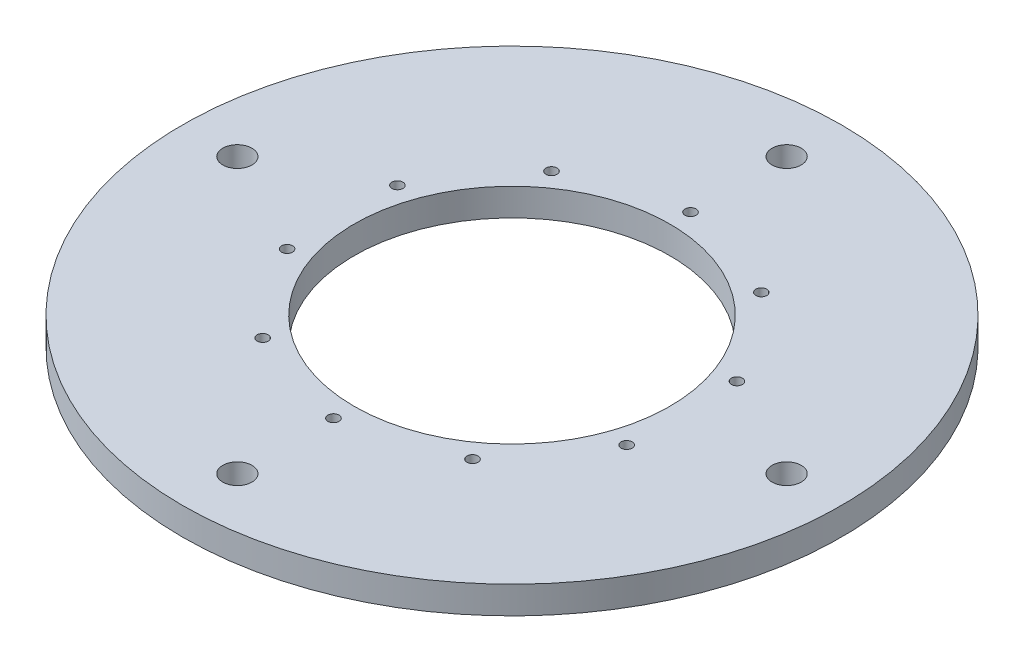
SolidWorks part; units mm, degrees
material "Plain Carbon Steel"
ref_plane "Front Plane" through (0, 0, 0) normal (0, 0, 1) x (1, 0, 0)
ref_plane "Top Plane" through (0, 0, 0) normal (0, 1, 0) x (1, 0, 0)
ref_plane "Right Plane" through (0, 0, 0) normal (1, 0, 0) x (0, 0, -1)
sketch "Sketch1" plane through (0, 0, 0) normal (0, 1, 0) x (1, 0, 0)
  circle A3 centre (0, 0) radius 152.4
  circle A8 centre (0, 0) radius 127 construction
  circle A20 centre (0, 0) radius 73.025
  circle A23 centre (0, 0) radius 82.55 construction
  point P2 (0, 127)
  point P5 (0, 82.55)
  dimension "Diameter_Takeout_BoltCircle" = 254
  dimension "Diameter_ThrustPlate" = 304.8
  dimension "D2" = 165.1
  dimension "D4" = 146.05
extrude "ThrustPlate_TC3" add sketch "Sketch1" against normal blind 12.7 separate body contours A3 region at (-148.0895, 0, 0)
sketch "Sketch11" plane through (0, 0, 0) normal (0, 1, 0) x (1, 0, 0)
  point P0 (0, 127)
hole_wizard "UNDEF_Clearance_ThrustPlate" positions "Sketch11" profile "Sketch12" hole size "1/2" standard "ANSI Inch" end condition through all
sketch "Sketch12" plane through (0, 0, -127) normal (1, 0, 0) x (0, 0, 1)
  line L0 (0, 0) -> (0, 12.7)
  line L1 (0, 12.7) -> (6.7462, 12.7)
  line L2 (6.7462, 12.7) -> (6.7462, 0)
  line L5 (6.7462, 0) -> (0, 0)
  line L11 (0, -6.35) -> (0, 107.95) construction
  dimension "Thru Hole Dia." = 13.4925
  dimension "Thru Hole Depth" = 12.7
pattern_circular "Clearance_ThrustPlate_Pattern" count 4 over 360 about axis through (0, -12.7, 0) along (0, 1, 0) of "UNDEF_Clearance_ThrustPlate" reverse direction yes
sketch "Sketch22" plane through (0, 0, 0) normal (0, 1, 0) x (1, 0, 0)
  point P0 (0, 82.55)
hole_wizard "#10 Clearance Hole1" positions "Sketch22" profile "Sketch23" hole size "#10" standard "ANSI Inch" end condition through all
sketch "Sketch23" plane through (0, 0, -82.55) normal (1, 0, 0) x (0, 0, 1)
  line L0 (0, 0) -> (0, 12.7)
  line L1 (0, 12.7) -> (2.5527, 12.7)
  line L2 (2.5527, 12.7) -> (2.5527, 0)
  line L5 (2.5527, 0) -> (0, 0)
  line L11 (0, -6.35) -> (0, 107.95) construction
  dimension "Thru Hole Dia." = 5.1054
  dimension "Thru Hole Depth" = 12.7
pattern_circular "CirPattern1" count 10 over 360 about axis through (0, -12.7, 0) along (0, 1, 0) of "#10 Clearance Hole1" reverse direction yes
equation "\"Diameter_BackPlate\"= 6.5"
equation "\"VAR_Diameter_BackPlate_BoltCircle\"= 6"
equation "\"VAR_Diameter_FuelOuterPlenum\"= 4.4"
equation "\"Thickness_ThrustPlate\"= 0.5'undetermined"
equation "\"Diameter_ThrustPlate\"= 12'defined"
equation "\"Diameter_Takeout_BoltCicle\"= 10'defined"
equation "\"Diameter_Takeout_BoltCircle@Sketch1\"=\"Diameter_Takeout_BoltCicle\""
equation "\"Diameter_ThrustPlate@Sketch1\"=\"Diameter_ThrustPlate\""
equation "\"D1@ThrustPlate_TC3\"=\"Thickness_ThrustPlate\""
equation "\"VAR_Diameter_CBORE\"= 0.44'undetermined"
equation "\"VAR_Diameter_Clearance_ThrustPlate\"= 0.25'undetermined"
equation "\"NumberBolts_BackPlate\"= 20"
equation "\"NumberBolts_Takeout\"= 4'defined"
equation "\"D1@Clearance_ThrustPlate_Pattern\"=\"NumberBolts_Takeout\""
